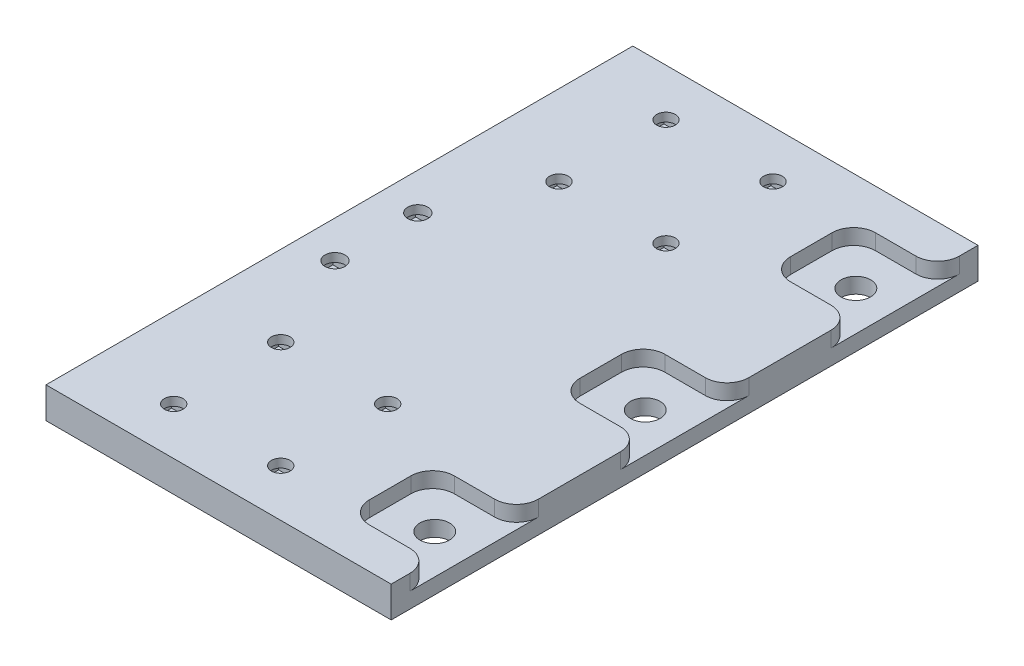
SolidWorks part; units mm, degrees
material "Onyx w/ CF"
ref_plane "Front Plane" through (0, 0, 0) normal (0, 0, 1) x (1, 0, 0)
ref_plane "Top Plane" through (0, 0, 0) normal (0, 1, 0) x (1, 0, 0)
ref_plane "Right Plane" through (0, 0, 0) normal (1, 0, 0) x (0, 0, -1)
sketch "Sketch1" plane through (0, 0, 0) normal (0, 1, 0) x (1, 0, 0)
  line L1 (-25, 47.5) -> (25, 47.5)
  line L2 (-25, 47.5) -> (-25, -47.5)
  line L3 (-25, -47.5) -> (25, -47.5)
  line L4 (25, 47.5) -> (25, -47.5)
  line L5 (-25, 47.5) -> (25, -47.5) construction
  line L6 (-25, -47.5) -> (25, 47.5) construction
  point P0 (0, 0)
  dimension "D1" = 50
  dimension "D2" = 95
extrude "Boss-Extrude1" add sketch "Sketch1" along normal mid plane 4.5
hole_wizard "M2.5 Clearance Hole1" positions "Sketch2" profile "Sketch3" hole size "M2.5" standard "ANSI Metric"
sketch "Sketch2" plane through (0, 2.25, 0) normal (0, 1, 0) x (1, 0, 0)
  line L1 (2.15, -20.15) -> (-13.35, -20.15)
  line L2 (2.15, -20.15) -> (2.15, -35.65)
  line L3 (2.15, -35.65) -> (-13.35, -35.65)
  line L4 (-13.35, -20.15) -> (-13.35, -35.65)
  line L5 (2.15, -20.15) -> (-13.35, -35.65) construction
  line L6 (2.15, -35.65) -> (-13.35, -20.15) construction
  line L9 (-25, -47.5) -> (25, -47.5) construction
  line L10 (-25, 47.5) -> (-25, -47.5) construction
  point P0 (2.15, -20.15)
  point P2 (2.15, -35.65)
  point P5 (-13.35, -35.65)
  point P8 (-13.35, -20.15)
  point P51 (-5.6, -27.9)
  dimension "D1" = 15.5
  dimension "D2" = 19.6
  dimension "D3" = 19.4
sketch "Sketch3" plane through (2.15, 2.25, 20.15) normal (1, 0, 0) x (0, 0, 1)
  line L0 (0, 0) -> (0, 7.1612)
  line L1 (0, 7.1612) -> (1.35, 6.35)
  line L2 (1.35, 6.35) -> (1.35, 0)
  line L5 (1.35, 0) -> (0, 0)
  line L10 (0, 7.1612) -> (-1.35, 6.35) construction
  line L11 (0, -6.35) -> (0, 107.95) construction
  dimension "Hole Dia." = 2.7
  dimension "Hole Depth" = 6.35
  dimension "Drill Angle" = 118
sketch "Sketch4" plane through (0, 2.25, 0) normal (0, 1, 0) x (1, 0, 0)
  line L0 (-25, -47.5) -> (25, -47.5) construction
  line L1 (-25, -47.5) -> (25, -47.5)
  line L2 (-25, -47.5) -> (-25, -42.5)
  line L3 (25, -47.5) -> (25, -42.5)
  line L4 (25, -42.5) -> (-25, -42.5)
  dimension "D1" = 5
extrude "Cut-Extrude1" cut sketch "Sketch4" against normal through all
mirror "Mirror1" about plane through (0, 0, 0) normal (0, 0, 1) of "Cut-Extrude1", "M2.5 Clearance Hole1"
sketch "Sketch5" plane through (0, 2.25, 0) normal (0, 1, 0) x (1, 0, 0)
  line L0 (25, -42.5) -> (25, 42.5) construction
  line L1 (25, -36.5) -> (16, -36.5) construction
  line L3 (25, -24.5) -> (16, -24.5) construction
  line L4 (13, -33.5) -> (13, -27.5) construction
  line L5 (22, -36.5) -> (16, -36.5) construction
  line L7 (25, -36.6524) -> (16, -36.6524)
  line L8 (12.8476, -33.5) -> (12.8476, -27.5)
  line L9 (25, -24.3476) -> (16, -24.3476)
  line L10 (25, 6.1524) -> (25, -6.1524)
  line L11 (25, -6.1524) -> (16, -6.1524)
  line L12 (12.8476, -3) -> (12.8476, 3)
  line L13 (25, 6.1524) -> (16, 6.1524)
  line L14 (25, 36.6524) -> (25, 24.3476)
  line L15 (25, 24.3476) -> (16, 24.3476)
  line L16 (12.8476, 27.5) -> (12.8476, 33.5)
  line L17 (25, 36.6524) -> (16, 36.6524)
  line L19 (22, -36.6524) -> (16, -36.6524) construction
  line L20 (25, -36.6524) -> (25, -24.3476)
  line L21 (25, -42.5) -> (-25, -42.5) construction
  arc A0 (16, -24.5) -> (13, -27.5) centre (16, -27.5) ccw construction
  arc A1 (16, -36.5) -> (13, -33.5) centre (16, -33.5) cw construction
  arc A4 (16, -36.6524) -> (12.8476, -33.5) centre (16, -33.5) cw
  arc A5 (16, -24.3476) -> (12.8476, -27.5) centre (16, -27.5) ccw
  arc A9 (16, -6.1524) -> (12.8476, -3) centre (16, -3) cw
  arc A10 (16, 6.1524) -> (12.8476, 3) centre (16, 3) ccw
  arc A13 (16, 24.3476) -> (12.8476, 27.5) centre (16, 27.5) cw
  arc A14 (16, 36.6524) -> (12.8476, 33.5) centre (16, 33.5) ccw
  point P11 (13, -24.5)
  point P14 (13, -36.5)
  point P27 (12.8476, -30.5)
  point P28 (12.8476, 0)
  dimension "D3" = 3
  dimension "D1" = 12
  dimension "D4" = 12
  dimension "D6" = 3
  dimension "D2" = 12
  dimension "D5" = 0.1524
  dimension "D7" = 30.5
extrude "Cut-Extrude2" cut sketch "Sketch5" against normal blind 2.25
hole_wizard "M4 Clearance Hole1" positions "Sketch6" profile "Sketch7" hole size "M4" standard "ANSI Metric"
sketch "Sketch6" plane through (0, 0, 0) normal (0, 1, 0) x (1, 0, 0)
  line L0 (12.8476, -27.5) -> (12.8476, -33.5) construction
  line L2 (12.8476, 3) -> (12.8476, -3) construction
  line L5 (12.8476, 33.5) -> (12.8476, 27.5) construction
  line L6 (12.8476, 0) -> (25, 0) construction
  line L7 (12.8476, 3) -> (12.8476, -3) construction
  line L8 (25, -6.1524) -> (25, 6.1524) construction
  point P0 (19.3048, -30.5)
  point P2 (19.3048, 0)
  point P4 (19.3048, 30.5)
  point P13 (12.8476, -30.5)
  point P21 (12.8476, 0)
  point P30 (12.8476, 30.5)
  dimension "D1" = 5.6952
sketch "Sketch7" plane through (19.3048, 0, 30.5) normal (1, 0, 0) x (0, 0, 1)
  line L0 (0, 0) -> (0, 11.3919)
  line L1 (0, 11.3919) -> (2.15, 10.1)
  line L2 (2.15, 10.1) -> (2.15, 0)
  line L5 (2.15, 0) -> (0, 0)
  line L10 (0, 11.3919) -> (-2.15, 10.1) construction
  line L11 (0, -6.35) -> (0, 107.95) construction
  dimension "Hole Dia." = 4.3
  dimension "Hole Depth" = 10.1
  dimension "Drill Angle" = 118
fillet "Fillet1" radius 3.1524 6 edges at (25, 1.125, -36.6524) (25, 1.125, -24.3476) (25, 1.125, -6.1524) (25, 1.125, 6.1524) (25, 1.125, 24.3476) (25, 1.125, 36.6524)
hole_wizard "M2.5 Clearance Hole2" positions "Sketch8" profile "Sketch9" hole size "M2.5" standard "ANSI Metric" end condition through all
sketch "Sketch8" plane through (0, -2.25, 0) normal (0, -1, 0) x (-1, 0, 0)
  line L0 (19.642, 6) -> (19.642, -6)
  line L2 (25, 42.5) -> (25, -42.5) construction
  point P0 (19.642, 6)
  point P2 (19.642, -6)
  point P10 (19.642, 0)
  dimension "D1" = 12
  dimension "D2" = 5.358
sketch "Sketch9" plane through (-19.642, -2.25, -6) normal (1, 0, 0) x (0, 0, -1)
  line L0 (0, 0) -> (0, 4.5)
  line L1 (0, 4.5) -> (1.45, 4.5)
  line L2 (1.45, 4.5) -> (1.45, 0)
  line L5 (1.45, 0) -> (0, 0)
  line L11 (0, -6.35) -> (0, 107.95) construction
  dimension "Thru Hole Dia." = 2.9
  dimension "Thru Hole Depth" = 4.5
sketch "Sketch10" plane through (0, 0, 0) normal (0, 1, 0) x (1, 0, 0)
  line L0 (-10.4726, -17.5726) -> (-10.4726, -22.7274)
  line L1 (-16.075, -17.725) -> (-10.625, -17.725) construction
  line L2 (-16.075, -17.725) -> (-16.075, -22.575) construction
  line L3 (-16.075, -22.575) -> (-10.625, -22.575) construction
  line L4 (-10.625, -17.725) -> (-10.625, -22.575) construction
  line L5 (-16.075, -17.725) -> (-10.625, -22.575) construction
  line L6 (-16.075, -22.575) -> (-10.625, -17.725) construction
  line L7 (-0.575, -17.725) -> (4.875, -17.725) construction
  line L8 (-0.575, -17.725) -> (-0.575, -22.575) construction
  line L9 (-0.575, -22.575) -> (4.875, -22.575) construction
  line L10 (4.875, -17.725) -> (4.875, -22.575) construction
  line L11 (-0.575, -17.725) -> (4.875, -22.575) construction
  line L12 (-0.575, -22.575) -> (4.875, -17.725) construction
  line L13 (-0.575, -33.225) -> (4.875, -33.225) construction
  line L14 (-0.575, -33.225) -> (-0.575, -38.075) construction
  line L15 (-0.575, -38.075) -> (4.875, -38.075) construction
  line L16 (4.875, -33.225) -> (4.875, -38.075) construction
  line L17 (-0.575, -33.225) -> (4.875, -38.075) construction
  line L18 (-0.575, -38.075) -> (4.875, -33.225) construction
  line L19 (-16.075, -33.225) -> (-10.625, -33.225) construction
  line L20 (-16.075, -33.225) -> (-16.075, -38.075) construction
  line L21 (-16.075, -38.075) -> (-10.625, -38.075) construction
  line L22 (-10.625, -33.225) -> (-10.625, -38.075) construction
  line L23 (-16.075, -33.225) -> (-10.625, -38.075) construction
  line L24 (-16.075, -38.075) -> (-10.625, -33.225) construction
  line L25 (-16.2274, -22.7274) -> (-10.4726, -22.7274)
  line L26 (-16.2274, -17.5726) -> (-16.2274, -22.7274)
  line L27 (-16.2274, -17.5726) -> (-10.4726, -17.5726)
  line L28 (-0.7274, -17.5726) -> (-0.7274, -22.7274)
  line L29 (-0.7274, -22.7274) -> (5.0274, -22.7274)
  line L30 (5.0274, -17.5726) -> (5.0274, -22.7274)
  line L31 (-0.7274, -17.5726) -> (5.0274, -17.5726)
  line L32 (-16.2274, -33.0726) -> (-10.4726, -33.0726)
  line L33 (-10.4726, -33.0726) -> (-10.4726, -38.2274)
  line L34 (-16.2274, -38.2274) -> (-10.4726, -38.2274)
  line L35 (-16.2274, -33.0726) -> (-16.2274, -38.2274)
  line L36 (-0.7274, -33.0726) -> (-0.7274, -38.2274)
  line L37 (-0.7274, -38.2274) -> (5.0274, -38.2274)
  line L38 (5.0274, -33.0726) -> (5.0274, -38.2274)
  line L39 (-0.7274, -33.0726) -> (5.0274, -33.0726)
  line L40 (-2.475, 0) -> (2.475, 0) construction
  line L41 (-16.075, 38.075) -> (-10.625, 33.225) construction
  line L42 (-16.075, 33.225) -> (-10.625, 38.075) construction
  line L43 (-10.625, 33.225) -> (-10.625, 38.075) construction
  line L44 (-16.075, 38.075) -> (-10.625, 38.075) construction
  line L45 (-16.075, 33.225) -> (-16.075, 38.075) construction
  line L46 (-16.075, 33.225) -> (-10.625, 33.225) construction
  line L47 (-0.575, 38.075) -> (4.875, 33.225) construction
  line L48 (-0.575, 33.225) -> (4.875, 38.075) construction
  line L49 (4.875, 33.225) -> (4.875, 38.075) construction
  line L50 (-0.575, 38.075) -> (4.875, 38.075) construction
  line L51 (-0.575, 33.225) -> (-0.575, 38.075) construction
  line L52 (-0.575, 33.225) -> (4.875, 33.225) construction
  line L53 (-0.575, 22.575) -> (4.875, 17.725) construction
  line L54 (-0.575, 17.725) -> (4.875, 22.575) construction
  line L55 (4.875, 17.725) -> (4.875, 22.575) construction
  line L56 (-0.575, 22.575) -> (4.875, 22.575) construction
  line L57 (-0.575, 17.725) -> (-0.575, 22.575) construction
  line L58 (-0.575, 17.725) -> (4.875, 17.725) construction
  line L59 (-16.075, 22.575) -> (-10.625, 17.725) construction
  line L60 (-16.075, 17.725) -> (-10.625, 22.575) construction
  line L61 (-10.625, 17.725) -> (-10.625, 22.575) construction
  line L62 (-16.075, 22.575) -> (-10.625, 22.575) construction
  line L63 (-16.075, 17.725) -> (-16.075, 22.575) construction
  line L64 (-16.075, 17.725) -> (-10.625, 17.725) construction
  line L65 (-0.7274, 33.0726) -> (5.0274, 33.0726)
  line L66 (5.0274, 33.0726) -> (5.0274, 38.2274)
  line L67 (-0.7274, 38.2274) -> (5.0274, 38.2274)
  line L68 (-0.7274, 33.0726) -> (-0.7274, 38.2274)
  line L69 (-16.2274, 33.0726) -> (-16.2274, 38.2274)
  line L70 (-16.2274, 38.2274) -> (-10.4726, 38.2274)
  line L71 (-10.4726, 33.0726) -> (-10.4726, 38.2274)
  line L72 (-16.2274, 33.0726) -> (-10.4726, 33.0726)
  line L73 (-0.7274, 17.5726) -> (5.0274, 17.5726)
  line L74 (5.0274, 17.5726) -> (5.0274, 22.7274)
  line L75 (-0.7274, 22.7274) -> (5.0274, 22.7274)
  line L76 (-0.7274, 17.5726) -> (-0.7274, 22.7274)
  line L77 (-16.2274, 17.5726) -> (-10.4726, 17.5726)
  line L78 (-16.2274, 17.5726) -> (-16.2274, 22.7274)
  line L79 (-16.2274, 22.7274) -> (-10.4726, 22.7274)
  line L80 (-10.4726, 17.5726) -> (-10.4726, 22.7274)
  line L86 (-22.5194, -3.4226) -> (-16.7646, -3.4226)
  line L87 (-22.5194, -3.4226) -> (-22.5194, -8.5774)
  line L88 (-22.5194, -8.5774) -> (-16.7646, -8.5774)
  line L89 (-16.7646, -3.4226) -> (-16.7646, -8.5774)
  line L90 (-22.5194, -3.4226) -> (-16.7646, -8.5774) construction
  line L91 (-22.5194, -8.5774) -> (-16.7646, -3.4226) construction
  line L92 (-22.5194, 8.5774) -> (-16.7646, 8.5774)
  line L93 (-22.5194, 8.5774) -> (-22.5194, 3.4226)
  line L94 (-22.5194, 3.4226) -> (-16.7646, 3.4226)
  line L95 (-16.7646, 8.5774) -> (-16.7646, 3.4226)
  line L96 (-22.5194, 8.5774) -> (-16.7646, 3.4226) construction
  line L97 (-22.5194, 3.4226) -> (-16.7646, 8.5774) construction
  point P0 (-13.35, -20.15)
  point P5 (2.15, -20.15)
  point P11 (2.15, -35.65)
  point P17 (-13.35, -35.65)
  point P23 (-19.642, -6)
  point P59 (-13.35, 35.65)
  point P75 (2.15, 35.65)
  point P77 (2.15, 20.15)
  point P78 (-13.35, 20.15)
  point P83 (-19.642, 6)
  dimension "D1" = 5.45
  dimension "D2" = 4.85
  dimension "D3" = 0.1524
extrude "Cut-Extrude3" cut sketch "Sketch10" against normal mid plane 2
